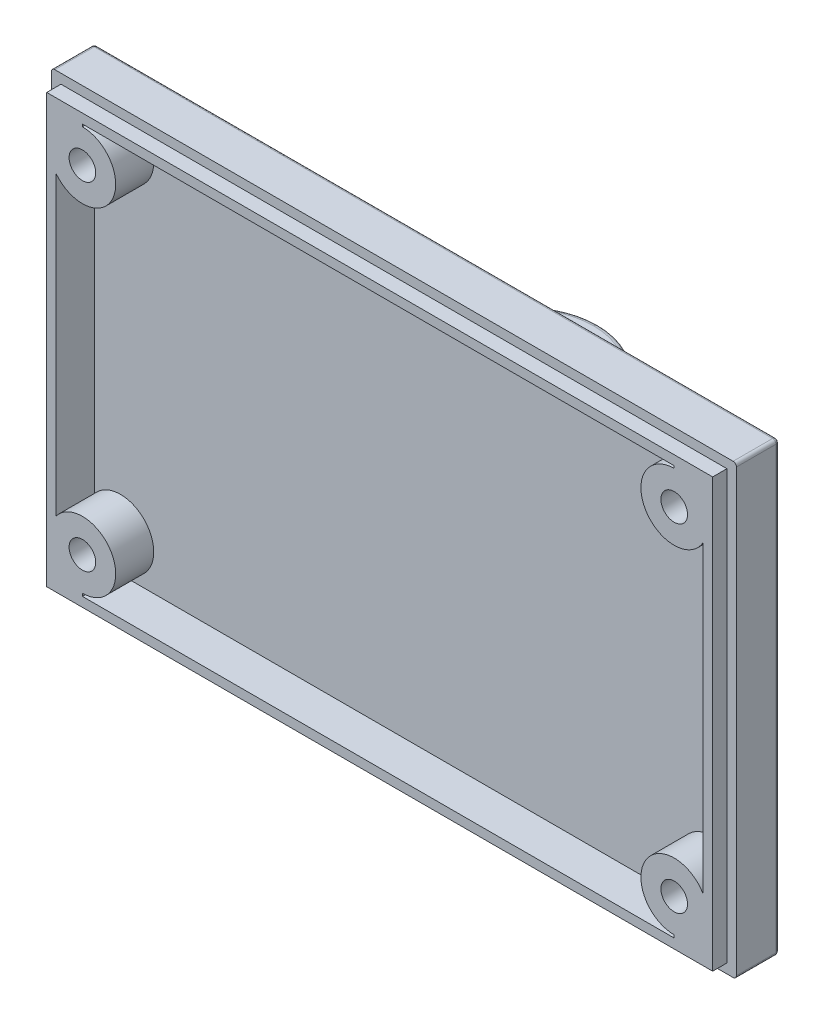
SolidWorks part; units mm, degrees
ref_plane "Front Plane" through (0, 0, 0) normal (0, 0, 1) x (1, 0, 0)
ref_plane "Top Plane" through (0, 0, 0) normal (0, 1, 0) x (1, 0, 0)
ref_plane "Right Plane" through (0, 0, 0) normal (1, 0, 0) x (0, 0, -1)
sketch "Sketch1" plane through (0, 0, 0) normal (0, 0, 1) x (1, 0, 0)
  line L1 (36, -23.5) -> (-36, -23.5)
  line L2 (36, -23.5) -> (36, 23.5)
  line L3 (36, 23.5) -> (-36, 23.5)
  line L4 (-36, -23.5) -> (-36, 23.5)
  line L5 (36, -23.5) -> (-36, 23.5) construction
  line L6 (36, 23.5) -> (-36, -23.5) construction
  point P0 (0, 0)
  dimension "D1" = 47
  dimension "D2" = 72
extrude "Boss-Extrude1" add sketch "Sketch1" along normal blind 6
shell "Shell1" thickness 2 removed face at (0, 0, 6)
sketch "Sketch3" plane through (0, 0, 6) normal (0, 0, 1) x (1, 0, 0)
  line L0 (36, 23.5) -> (-36, 23.5) construction
  line L1 (35, -22.5) -> (-35, -22.5)
  line L2 (35, -22.5) -> (35, 22.5)
  line L3 (35, 22.5) -> (-35, 22.5)
  line L4 (-35, -22.5) -> (-35, 22.5)
  line L5 (35, -22.5) -> (-35, 22.5) construction
  line L6 (35, 22.5) -> (-35, -22.5) construction
  line L7 (-36, 23.5) -> (-36, -23.5) construction
  point P0 (0, 0)
  dimension "D1" = 1
  dimension "D2" = 1
extrude "Cut-Extrude1" cut sketch "Sketch3" against normal blind 1.5 flip side to cut
sketch "Sketch2" plane through (0, 0, 2) normal (0, 0, 1) x (1, 0, 0)
  line L0 (-34, 21.5) -> (-34, -21.5) construction
  line L1 (34, 21.5) -> (-34, 21.5) construction
  circle A0 centre (-31.25, 17.75) radius 3.5
  circle A1 centre (30.96, 17.75) radius 3.5
  circle A2 centre (-31.25, -17.71) radius 3.5
  circle A3 centre (30.96, -17.71) radius 3.5
  dimension "D1" = 7
  dimension "D2" = 2.75
  dimension "D3" = 3.75
  dimension "D4" = 2
  dimension "D5" = 2
extrude "Boss-Extrude2" add sketch "Sketch2" along normal blind 4
sketch "Sketch4" plane through (0, 0, 2) normal (0, 0, 1) x (1, 0, 0)
  line L1 (-34, -21.5) -> (-31.25, -21.5)
  line L2 (-34, -21.5) -> (-34, -17.71)
  line L3 (-34, -17.71) -> (-31.25, -17.71)
  line L4 (-31.25, -21.5) -> (-31.25, -17.71)
  line L5 (-34, 21.5) -> (-31.25, 21.5)
  line L6 (-34, 21.5) -> (-34, 17.75)
  line L7 (-34, 17.75) -> (-31.25, 17.75)
  line L8 (-31.25, 21.5) -> (-31.25, 17.75)
  line L9 (34, 21.5) -> (30.96, 21.5)
  line L10 (34, 21.5) -> (34, 17.75)
  line L11 (34, 17.75) -> (30.96, 17.75)
  line L12 (30.96, 21.5) -> (30.96, 17.75)
  line L13 (34, -21.5) -> (30.96, -21.5)
  line L14 (34, -21.5) -> (34, -17.71)
  line L15 (34, -17.71) -> (30.96, -17.71)
  line L16 (30.96, -21.5) -> (30.96, -17.71)
  circle A0 centre (-31.25, -17.71) radius 3.5 construction
  circle A1 centre (-31.25, 17.75) radius 3.5 construction
  dimension "D1" = 0
  dimension "D2" = 0
  dimension "D3" = 0
extrude "Boss-Extrude3" add sketch "Sketch4" along normal blind 4
sketch "Sketch5" plane through (0, 0, 6) normal (0, 0, 1) x (1, 0, 0)
  circle A0 centre (30.96, -17.71) radius 1.4
  circle A1 centre (30.96, 17.75) radius 1.4
  circle A2 centre (-31.25, -17.71) radius 1.4
  circle A3 centre (-31.25, 17.75) radius 1.4
  arc A4 (30.96, 21.25) -> (34, 16.0155) centre (30.96, 17.75) ccw construction
  dimension "D1" = 2.8
  dimension "D2" = 2.8
  dimension "D4" = 2.8
  dimension "D5" = 2.8
  dimension "D3" = 0
extrude "Cut-Extrude2" cut sketch "Sketch5" against normal through all
sketch "Sketch6" plane through (0, 0, 0) normal (0, 0, -1) x (-1, 0, 0)
  circle A0 centre (31.25, 17.75) radius 2.75
  circle A1 centre (-30.96, 17.75) radius 2.75
  circle A2 centre (31.25, -17.71) radius 2.75
  circle A3 centre (-30.96, -17.71) radius 2.75
  dimension "D1" = 5.5
  dimension "D2" = 2
  dimension "D3" = 2
extrude "Cut-Extrude3" cut sketch "Sketch6" against normal blind 3
sketch "Sketch7" plane through (0, 0, 0) normal (0, 0, -1) x (-1, 0, 0)
  line L1 (8, -1.5) -> (-8, -1.5)
  line L2 (8, -1.5) -> (8, 1.5)
  line L3 (8, 1.5) -> (-8, 1.5)
  line L4 (-8, -1.5) -> (-8, 1.5)
  line L5 (8, -1.5) -> (-8, 1.5) construction
  line L6 (8, 1.5) -> (-8, -1.5) construction
  line L7 (8, 4.5) -> (-8, 4.5)
  line L8 (8, 4.5) -> (8, 7.5)
  line L9 (8, 7.5) -> (-8, 7.5)
  line L10 (-8, 4.5) -> (-8, 7.5)
  line L11 (8, -4.5) -> (-8, -4.5)
  line L12 (8, -4.5) -> (8, -7.5)
  line L13 (8, -7.5) -> (-8, -7.5)
  line L14 (-8, -4.5) -> (-8, -7.5)
  point P0 (0, 0)
  dimension "D1" = 3
  dimension "D2" = 16
  dimension "D3" = 3
  dimension "D4" = 3
  dimension "D5" = 3
  dimension "D6" = 3
extrude "Boss-Extrude5" add sketch "Sketch7" along normal blind 17
fillet "Fillet2" radius 8 6 edges at (8, -6, -17) (8, 0, -17) (8, 6, -17) (-8, 6, -17) (-8, 0, -17) (-8, -6, -17)
sketch "Sketch9" plane through (0, -7.5, 0) normal (0, -1, 0) x (1, 0, 0)
  circle A0 centre (0, -9) radius 1.5
  dimension "D2" = 3
  dimension "D1" = 8
extrude "Cut-Extrude5" cut sketch "Sketch9" against normal through all
fillet "Fillet3" radius 0.35 4 edges at (36, 0, 0) (0, -23.5, 0) (-36, 0, 0) (0, 23.5, 0)
fillet "Fillet4" radius 0.5 24 edges at (-8, 7.5, -4.5) (-5.6569, 7.5, -14.6569) (5.6569, 7.5, -14.6569) (-8, 1.5, -4.5) (-5.6569, 1.5, -14.6569) (5.6569, 1.5, -14.6569) (-8, 4.5, -4.5) (-5.6569, 4.5, -14.6569) (5.6569, 4.5, -14.6569) (-8, -1.5, -4.5) (-5.6569, -1.5, -14.6569) (5.6569, -1.5, -14.6569) (8, -7.5, -4.5) (5.6569, -7.5, -14.6569) (-5.6569, -7.5, -14.6569) (8, -4.5, -4.5) (5.6569, -4.5, -14.6569) (-5.6569, -4.5, -14.6569) (8, 7.5, -4.5) (8, 1.5, -4.5) (8, 4.5, -4.5) (8, -1.5, -4.5) (-8, -7.5, -4.5) (-8, -4.5, -4.5)
fillet "Fillet5" radius 0.8 24 edges at (-7.8536, -4.6464, 0) (-8, -6, 0) (-7.8536, -7.3536, 0) (0, -7.5, 0) (7.8536, -7.3536, 0) (8, -6, 0) (7.8536, -4.6464, 0) (-7.8536, 1.3536, 0) (-8, 0, 0) (-7.8536, -1.3536, 0) (0, -1.5, 0) (7.8536, -1.3536, 0) (8, 0, 0) (7.8536, 1.3536, 0) (-7.8536, 7.3536, 0) (-8, 6, 0) (-7.8536, 4.6464, 0) (0, 4.5, 0) (7.8536, 4.6464, 0) (8, 6, 0) (7.8536, 7.3536, 0) (0, -4.5, 0) (0, 1.5, 0) (0, 7.5, 0)
fillet "Fillet6" radius 0.35 8 edges at (-35.8975, 23.3975, 0.1025) (35.8975, 23.3975, 0.1025) (35.8975, -23.3975, 0.1025) (-35.8975, -23.3975, 0.1025) (-36, 23.5, 2.425) (36, 23.5, 2.425) (36, -23.5, 2.425) (-36, -23.5, 2.425)
